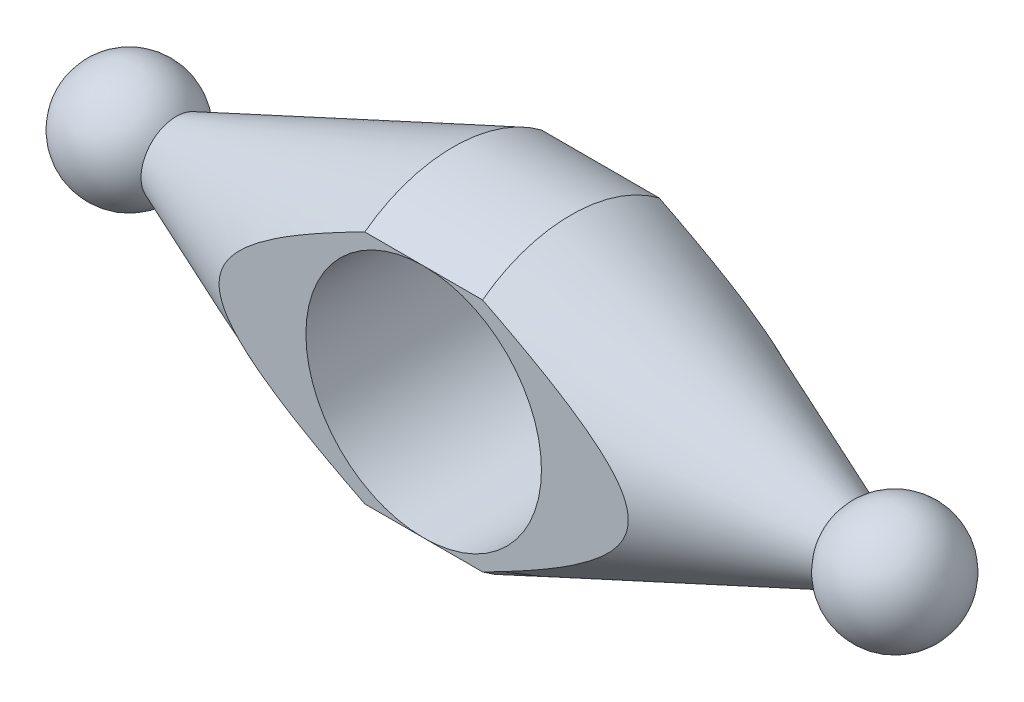
SolidWorks part; units mm, degrees
ref_plane "Спереди" through (0, 0, 0) normal (0, 0, 1) x (1, 0, 0)
ref_plane "Сверху" through (0, 0, 0) normal (0, 1, 0) x (1, 0, 0)
ref_plane "Справа" through (0, 0, 0) normal (1, 0, 0) x (0, 0, -1)
other "Configuration Table"
sketch "Эскиз1" plane through (0, 0, 0) normal (0, 0, 1) x (1, 0, 0)
  line L0 (0, 0) -> (301.8185, 0) construction
  line L1 (9, 3) -> (32.5, 12.5)
  line L2 (32.5, 12.5) -> (42.5, 12.5)
  line L3 (37.5, 12.5) -> (37.5, 24.2241) construction
  line L4 (66, 3) -> (42.5, 12.5)
  line L5 (0, 0) -> (75, 0)
  arc A0 (0, 0) -> (9, 3) centre (5, 0) cw
  arc A1 (75, 0) -> (66, 3) centre (70, 0) ccw
  dimension "D1" = 5
  dimension "D5" = 6
  dimension "D2" = 37.5
  dimension "D3" = 25
  dimension "D4" = 5
revolve "Повернуть1" add sketch "Эскиз1" angle 360 about L5
sketch "Эскиз2" plane through (0, 0, 0) normal (0, 0, 1) x (1, 0, 0)
  line L0 (0, 0) -> (79.6493, 0) construction
  line L1 (37.5, 0) -> (37.5, 26.1641) construction
  dimension "D1" = 37.5
ref_plane "Плоскость1" through (37.5, 0, 0) normal (1, 0, 0) x (0, 0, -1)
sketch "Эскиз4" plane through (37.5, 0, 0) normal (1, 0, 0) x (0, 0, -1)
  line L0 (-7.5, 10) -> (7.5, 10)
  line L1 (0, 0) -> (0, 26.1641) construction
  line L2 (7.5, 10) -> (7.5, 20)
  line L3 (7.5, 20) -> (15, 20)
  line L4 (15, 20) -> (15, 0)
  line L5 (0, 0) -> (29.9402, 0) construction
  line L6 (0, 0) -> (0, 17.1635) construction
  line L7 (-15, 20) -> (-15, 0)
  line L8 (-7.5, 20) -> (-15, 20)
  line L9 (-7.5, 10) -> (-7.5, 20)
  line L10 (15, 0) -> (-15, 0)
  point P15 (0, 10)
  dimension "D1" = 20
  dimension "D2" = 7.5
  dimension "D3" = 40
  dimension "D4" = 15
revolve "Вырез-Повернуть1" cut sketch "Эскиз4" angle 360 about L5
